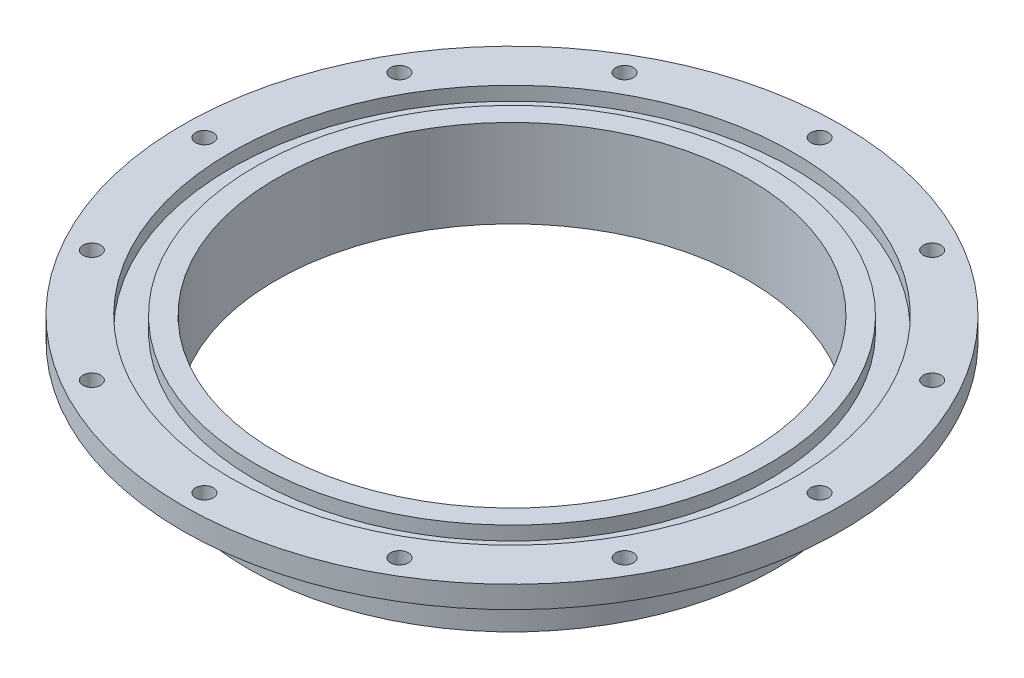
SolidWorks part; units mm, degrees
ref_plane "Front Plane" through (0, 0, 0) normal (0, 0, 1) x (1, 0, 0)
ref_plane "Top Plane" through (0, 0, 0) normal (0, 1, 0) x (1, 0, 0)
ref_plane "Right Plane" through (0, 0, 0) normal (1, 0, 0) x (0, 0, -1)
sketch "Sketch1" plane through (0, 0, 0) normal (0, 1, 0) x (1, 0, 0)
  circle A0 centre (0, 0) radius 76.2
  circle A1 centre (0, 0) radius 68.2625
  dimension "D1" = 152.4
  dimension "D2" = 7.9375
extrude "Inner Cylinder" add sketch "Sketch1" along normal blind 19.05
sketch "Sketch2" plane through (0, 19.05, 0) normal (0, 1, 0) x (1, 0, 0)
  circle A0 centre (0, 0) radius 68.2625
  circle A1 centre (0, 0) radius 68.2625 construction
  circle A2 centre (0, 0) radius 95.25
  dimension "D1" = 190.5
extrude "Flange" add sketch "Sketch2" along normal blind 6.35
sketch "Sketch4" plane through (0, 25.4, 0) normal (0, 1, 0) x (1, 0, 0)
  line L0 (0, 75.8825) -> (0, 81.2165) construction
  circle A3 centre (0, 0) radius 81.407
  circle A4 centre (0, 0) radius 74.295
  point P7 (0, 78.5495)
  dimension "D1" = 148.59
  dimension "D2" = 7.112
  dimension "D3" = 2.667
extrude "Groove" cut sketch "Sketch4" against normal blind 3.9878
sketch "Sketch5" plane through (0, 25.4, 0) normal (0, 1, 0) x (1, 0, 0)
  line L0 (82.55, 0) -> (95.25, 0) construction
  circle A0 centre (0, 0) radius 88.9 construction
  circle A1 centre (0, -88.9) radius 3.175 construction
  circle A3 centre (0, -88.9) radius 2.5527
  circle A6 centre (0, 0) radius 82.55 construction
  circle A7 centre (0, 0) radius 95.25 construction
  point P9 (88.9, 0)
  dimension "D1" = 5.1054
  dimension "D2" = 165.1
  dimension "D3" = 6.35
extrude "Screw Holes" cut sketch "Sketch5" against normal up to surface (6.35 mm away) up to face at (0, 19.05, 76.2)
pattern_circular "CirPattern1" count 12 over 360 about axis through (0, 25.4, 0) along (0, 1, 0) of "Screw Holes"
sketch "Sketch6" plane through (0, 25.4, 0) normal (0, 1, 0) x (1, 0, 0)
  circle A0 centre (0, 0) radius 82.55
  dimension "D1" = 165.1
ref_plane "Plane1" through (0, 9.525, 0) normal (0, -1, 0) x (-1, 0, 0)
sketch "Sketch7" plane through (0, 9.525, 0) normal (0, -1, 0) x (-1, 0, 0)
  circle A0 centre (0, 0) radius 76.2
  circle A1 centre (0, 0) radius 76.2 construction
  circle A2 centre (0, 0) radius 71.8566
  dimension "D1" = 4.3434
extrude "Cut-Extrude1" cut sketch "Sketch7" against normal blind 3.6068 and the other way blind 3.6068
